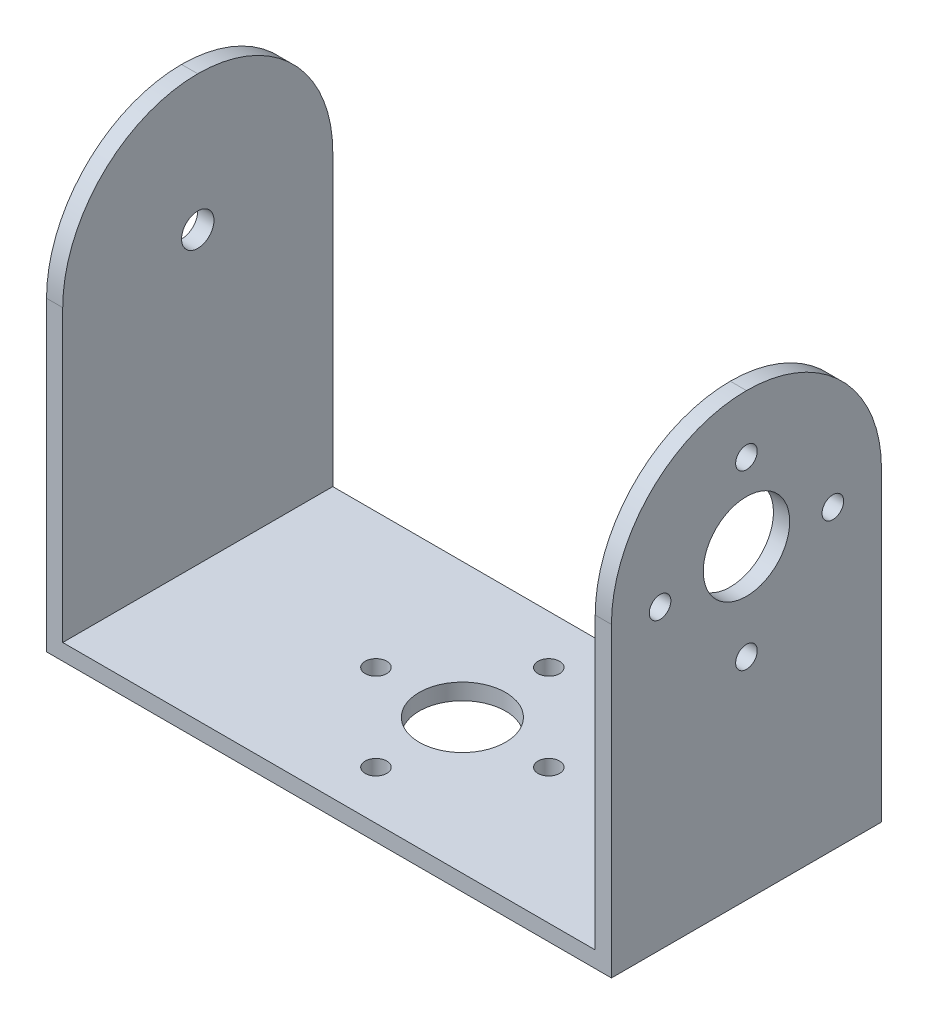
SolidWorks part; units mm, degrees
ref_plane "Front" through (0, 0, 0) normal (0, 0, 1) x (1, 0, 0)
ref_plane "Top" through (0, 0, 0) normal (0, 1, 0) x (1, 0, 0)
ref_plane "Right" through (0, 0, 0) normal (1, 0, 0) x (0, 0, -1)
sketch "Sketch1" plane through (0, 0, 0) normal (0, 0, 1) x (1, 0, 0)
  line L0 (0, 40.85) -> (1.5, 40.85)
  line L1 (50.8, 40.85) -> (52.3, 40.85)
  line L3 (0, 0) -> (0, 40.85)
  line L4 (0, 0) -> (52.3, 0)
  line L5 (52.3, 0) -> (52.3, 40.85)
  line L6 (1.5, 1.5) -> (1.5, 40.85)
  line L7 (1.5, 1.5) -> (50.8, 1.5)
  line L8 (50.8, 1.5) -> (50.8, 40.85)
  dimension "D1" = 1.5
  dimension "D2" = 1.5
  dimension "D3" = 1.5
  dimension "D4" = 52.3
  dimension "D5" = 40.85
  dimension "D6" = 40.85
extrude "Boss-Extrude1" add sketch "Sketch1" against normal blind 25
fillet "Fillet1" radius 12.5 4 edges at (0.75, 40.85, 0) (51.55, 40.85, 0) (0.75, 40.85, -25) (51.55, 40.85, -25)
sketch "Sketch3" plane through (0, 1.5, 0) normal (0, 1, 0) x (1, 0, 0)
  circle A0 centre (26, 12.5) radius 4
  circle A1 centre (34, 12.5) radius 1
  circle A2 centre (26, 20.5) radius 1
  circle A3 centre (26, 4.5) radius 1
  circle A4 centre (18, 12.5) radius 1
  point P13 (26, 12.5)
  dimension "D1" = 4
extrude "Cut-Extrude2" cut sketch "Sketch3" against normal through all contours A0 | A1 | A2 | A4 | A4 | A3 region at (26, 1.5, -12.5) region at (34, 1.5, -12.5) region at (26, 1.5, -20.5) region at (18, 1.5, -12.5)
sketch "Sketch4" plane through (52.3, 0, 0) normal (1, 0, 0) x (0, 0, -1)
  circle A0 centre (12.5, 28.35) radius 4
  circle A1 centre (20.5, 27.5) radius 1
  circle A2 centre (12.5, 35.5) radius 1
  circle A3 centre (12.5, 19.5) radius 1
  circle A4 centre (4.5, 27.5) radius 1
extrude "Cut-Extrude3" cut sketch "Sketch4" against normal blind 25
sketch "Sketch5" plane through (0, 0, 0) normal (-1, 0, 0) x (0, 0, 1)
  circle A0 centre (-12.5, 28.35) radius 1.5
extrude "Cut-Extrude4" cut sketch "Sketch5" against normal blind 25 contours A0
